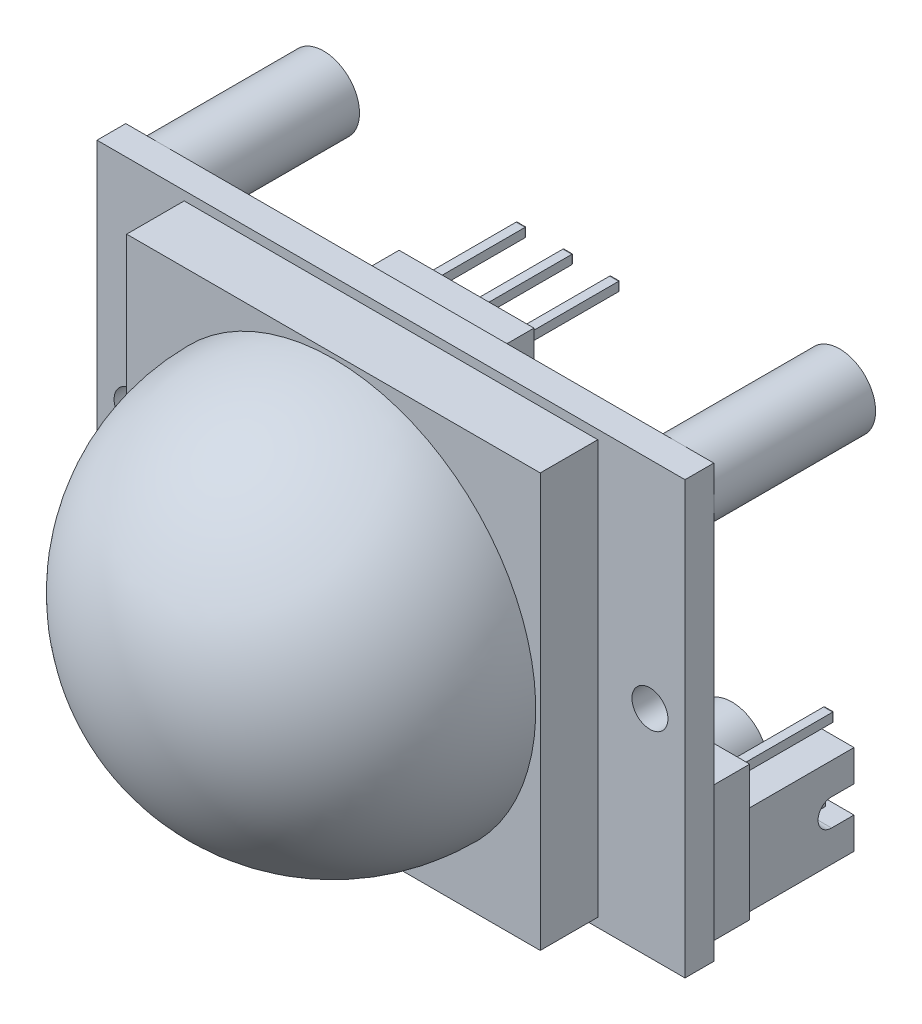
SolidWorks part; units mm, degrees
ref_plane "Front Plane" through (0, 0, 0) normal (0, 0, 1) x (1, 0, 0)
ref_plane "Top Plane" through (0, 0, 0) normal (0, 1, 0) x (1, 0, 0)
ref_plane "Right Plane" through (0, 0, 0) normal (1, 0, 0) x (0, 0, -1)
sketch "Sketch2" plane through (0, 0, 0) normal (0, 0, 1) x (1, 0, 0)
  line L1 (-16.35, 12) -> (16.35, 12)
  line L2 (-16.35, 12) -> (-16.35, -12)
  line L3 (-16.35, -12) -> (16.35, -12)
  line L4 (16.35, 12) -> (16.35, -12)
  line L5 (-16.35, 12) -> (16.35, -12) construction
  line L6 (-16.35, -12) -> (16.35, 12) construction
  point P0 (0, 0)
  dimension "D1" = 32.7
  dimension "D2" = 24
extrude "Boss-Extrude1" add sketch "Sketch2" along normal blind 1.6
sketch "Sketch3" plane through (0, 0, 1.6) normal (0, 0, 1) x (1, 0, 0)
  line L1 (-11.5, 11.5) -> (11.5, 11.5)
  line L2 (-11.5, 11.5) -> (-11.5, -11.5)
  line L3 (-11.5, -11.5) -> (11.5, -11.5)
  line L4 (11.5, 11.5) -> (11.5, -11.5)
  line L5 (-11.5, 11.5) -> (11.5, -11.5) construction
  line L6 (-11.5, -11.5) -> (11.5, 11.5) construction
  point P0 (0, 0)
  dimension "D1" = 23
  dimension "D2" = 23
extrude "Boss-Extrude2" add sketch "Sketch3" along normal blind 3.2
sketch "Sketch4" plane through (0, 0, 4.8) normal (0, 0, 1) x (1, 0, 0)
  circle A0 centre (0, 0) radius 11.25
  dimension "D1" = 22.5
sketch "Sketch5" plane through (0, 0, 0) normal (1, 0, 0) x (0, 0, -1)
  line L0 (-1.6, 0) -> (-16.1, 0) construction
  line L1 (-1.6, -11.5) -> (-1.6, 11.5) construction
  line L2 (-4.825, -0.025) -> (-16.1, 0)
  line L3 (-4.825, -0.025) -> (-4.8, 0)
  line L4 (-1.6, 0) -> (-16.1, 0) construction
  line L5 (-1.6, 0) -> (-4.8, 0) construction
  line L6 (-4.8, 11.25) -> (-4.8, -11.25) construction
  line L7 (-4.8, 0) -> (-4.8, 11.25)
  arc A0 (-4.8, 11.25) -> (-16.1, 0) centre (-4.825, -0.025) ccw
  dimension "D3" = 11.275
  dimension "D1" = 14.5
  dimension "D2" = 11.25
revolve "Revolve2" add sketch "Sketch5" angle 360 about L2
sketch "Sketch6" plane through (0, 0, 1.6) normal (0, 0, 1) x (1, 0, 0)
  line L0 (-16.35, 0) -> (16.35, 0) construction
  line L1 (-16.35, 12) -> (-16.35, -12) construction
  line L2 (16.35, -12) -> (16.35, 12) construction
  line L3 (-14.4, 0) -> (14.4, 0) construction
  circle A0 centre (-14.4, 0) radius 1
  circle A1 centre (14.4, 0) radius 1
  point P10 (0, 0)
  dimension "D1" = 2
  dimension "D2" = 28.8
extrude "Cut-Extrude1" cut sketch "Sketch6" against normal through all
sketch "Sketch7" plane through (0, 0, 0) normal (0, 0, -1) x (-1, 0, 0)
  line L0 (-16.35, 12) -> (16.35, 12) construction
  line L2 (-16.35, -12) -> (-16.35, 12) construction
  line L3 (16.35, 12) -> (16.35, -12) construction
  line L4 (16.35, -12) -> (-16.35, -12) construction
  line L5 (-6.35, -4.6849) -> (-6.35, -14.4498) construction
  circle A0 centre (-14.35, 10) radius 2
  circle A1 centre (14.35, 10) radius 2
  circle A2 centre (14.35, -10) radius 2
  circle A3 centre (-8.35, -10) radius 2
  dimension "D1" = 4
  dimension "D2" = 10
extrude "Boss-Extrude4" add sketch "Sketch7" along normal blind 9
sketch "Sketch8" plane through (0, 0, -9) normal (0, 0, -1) x (-1, 0, 0)
  circle A0 centre (14.35, 10) radius 1
  circle A1 centre (-14.35, 10) radius 1
  arc A2 (-16.35, 10) -> (-14.35, 12) centre (-14.35, 10) ccw construction
  circle A3 centre (14.35, -10) radius 1
  circle A4 centre (14.35, -10) radius 2 construction
  circle A5 centre (-8.35, -10) radius 1
  circle A6 centre (-8.35, -10) radius 2 construction
  dimension "D1" = 2
extrude "Cut-Extrude2" cut sketch "Sketch8" against normal blind 0.3
sketch "Sketch9" plane through (0, 0, 0) normal (0, 0, -1) x (-1, 0, 0)
  line L1 (-9.35, 7.4) -> (-5.35, 7.4)
  line L2 (-9.35, 7.4) -> (-9.35, -3)
  line L3 (-9.35, -3) -> (-5.35, -3)
  line L4 (-5.35, 7.4) -> (-5.35, -3)
  line L5 (-16.35, -12) -> (-16.35, 10) construction
  line L6 (-14.35, 12) -> (14.35, 12) construction
  dimension "D1" = 11
  dimension "D2" = 4.6
  dimension "D3" = 4
  dimension "D4" = 15
extrude "Boss-Extrude5" add sketch "Sketch9" along normal blind 1.5
sketch "Sketch10" plane through (0, 0, 0) normal (0, 0, -1) x (-1, 0, 0)
  line L0 (16.35, 10) -> (16.35, -10) construction
  line L1 (9.85, 4.5) -> (14.35, 4.5)
  line L2 (9.85, 4.5) -> (9.85, 2)
  line L3 (9.85, 2) -> (14.35, 2)
  line L4 (14.35, 4.5) -> (14.35, 2)
  line L5 (-14.35, 12) -> (14.35, 12) construction
  dimension "D1" = 4.5
  dimension "D2" = 2.5
  dimension "D3" = 6.5
  dimension "D4" = 10
extrude "Boss-Extrude6" add sketch "Sketch10" along normal blind 1.5
sketch "Sketch11" plane through (0, 0, 0) normal (0, 0, -1) x (-1, 0, 0)
  line L0 (-16.35, -12) -> (-16.35, 10) construction
  line L1 (-3.85, 11) -> (3.65, 11)
  line L2 (-3.85, 11) -> (-3.85, 8.5)
  line L3 (-3.85, 8.5) -> (3.65, 8.5)
  line L4 (3.65, 11) -> (3.65, 8.5)
  line L5 (-14.35, 12) -> (14.35, 12) construction
  dimension "D1" = 2.5
  dimension "D2" = 7.5
  dimension "D3" = 20
  dimension "D4" = 1
extrude "Boss-Extrude7" add sketch "Sketch11" along normal blind 2.5
sketch "Sketch12" plane through (0, 0, -2.5) normal (0, 0, -1) x (-1, 0, 0)
  line L0 (-3.85, 9.75) -> (3.65, 9.75) construction
  line L1 (-3.85, 11) -> (-3.85, 8.5) construction
  line L2 (3.65, 8.5) -> (3.65, 11) construction
  line L3 (-0.1, 8.5) -> (-0.1, 11) construction
  line L4 (-3.85, 8.5) -> (3.65, 8.5) construction
  line L5 (3.65, 11) -> (-3.85, 11) construction
  line L6 (2.75, 9.75) -> (-2.95, 9.75) construction
  line L7 (-0.35, 10) -> (0.15, 10)
  line L8 (-0.35, 10) -> (-0.35, 9.5)
  line L9 (-0.35, 9.5) -> (0.15, 9.5)
  line L10 (0.15, 10) -> (0.15, 9.5)
  line L11 (-0.35, 10) -> (0.15, 9.5) construction
  line L12 (-0.35, 9.5) -> (0.15, 10) construction
  line L13 (-2.95, 10) -> (-2.45, 10)
  line L14 (-2.95, 10) -> (-2.95, 9.5)
  line L15 (-2.95, 9.5) -> (-2.45, 9.5)
  line L16 (-2.45, 10) -> (-2.45, 9.5)
  line L17 (-2.95, 10) -> (-2.45, 9.5) construction
  line L18 (-2.95, 9.5) -> (-2.45, 10) construction
  line L19 (2.25, 10) -> (2.75, 10)
  line L20 (2.25, 10) -> (2.25, 9.5)
  line L21 (2.25, 9.5) -> (2.75, 9.5)
  line L22 (2.75, 10) -> (2.75, 9.5)
  line L23 (2.25, 10) -> (2.75, 9.5) construction
  line L24 (2.25, 9.5) -> (2.75, 10) construction
  point P12 (-0.1, 9.75)
  point P20 (-0.1, 9.75)
  point P21 (-2.7, 9.75)
  point P26 (-2.7, 9.75)
  point P27 (2.5, 9.75)
  point P32 (2.5, 9.75)
  dimension "D1" = 0.5
  dimension "D2" = 0.5
  dimension "D3" = 5.7
extrude "Boss-Extrude8" add sketch "Sketch12" along normal blind 5.7
fillet "Fillet1" radius 0.1 12 edges at (-2.5, 9.5, -8.2) (-2.25, 9.75, -8.2) (-2.5, 10, -8.2) (-2.75, 9.75, -8.2) (0.1, 9.5, -8.2) (-0.15, 9.75, -8.2) (0.1, 10, -8.2) (0.35, 9.75, -8.2) (2.7, 9.5, -8.2) (2.95, 9.75, -8.2) (2.45, 9.75, -8.2) (2.7, 10, -8.2)
sketch "Sketch13" plane through (0, 0, 0) normal (0, 0, -1) x (-1, 0, 0)
  line L0 (-16.35, -12) -> (-16.35, 10) construction
  line L1 (-13.35, -11.5) -> (-15.85, -11.5)
  line L2 (-13.35, -11.5) -> (-13.35, -4)
  line L3 (-13.35, -4) -> (-15.85, -4)
  line L4 (-15.85, -11.5) -> (-15.85, -4)
  line L5 (-8.35, -12) -> (-16.35, -12) construction
  dimension "D1" = 7.5
  dimension "D2" = 2.5
  dimension "D3" = 0.5
  dimension "D4" = 0.5
extrude "Boss-Extrude9" add sketch "Sketch13" along normal blind 2.5
sketch "Sketch14" plane through (0, 0, -2.5) normal (0, 0, -1) x (-1, 0, 0)
  line L0 (-15.85, -4) -> (-15.85, -11.5) construction
  line L1 (-13.15, -11.3) -> (-15.65, -11.3)
  line L2 (-13.15, -11.3) -> (-13.15, -6.3)
  line L3 (-13.15, -6.3) -> (-15.65, -6.3)
  line L4 (-15.65, -11.3) -> (-15.65, -6.3)
  line L7 (-15.85, -11.5) -> (-13.35, -11.5) construction
  dimension "D1" = 5
  dimension "D2" = 2.5
  dimension "D3" = 0.2
  dimension "D4" = 0.2
extrude "Boss-Extrude10" add sketch "Sketch14" along normal blind 6
sketch "Sketch17" plane through (15.65, 0, 0) normal (1, 0, 0) x (0, 0, -1)
  line L0 (8.5, -8.8) -> (2.5, -8.8) construction
  line L1 (8.5, -6.3) -> (8.5, -11.3) construction
  line L2 (2.5, -6.3) -> (2.5, -11.3) construction
  line L3 (8.5, -8.8) -> (6.5, -8.8) construction
  line L4 (8.5, -8.05) -> (7.3244, -8.05)
  line L5 (8.5, -8.05) -> (8.5, -9.55)
  line L6 (8.5, -9.55) -> (7.3244, -9.55)
  line L7 (7.3244, -8.05) -> (7.3244, -8.0537)
  line L10 (6.5, -7.0903) -> (6.5, -10.3644) construction
  line L11 (5.5, -8.8) -> (4.6684, -8.8) construction
  line L12 (7.3244, -9.5463) -> (7.3244, -9.55)
  line L13 (7.3276, -8.054) -> (7.3244, -8.05) construction
  line L14 (7.3276, -9.546) -> (7.3244, -9.55) construction
  arc A3 (7.3276, -8.054) -> (7.3244, -8.0537) centre (7.25, -8.8) ccw
  arc A4 (7.3276, -8.054) -> (7.3244, -8.0537) centre (7.25, -8.8) ccw
  arc A5 (7.3244, -9.5463) -> (7.3276, -9.546) centre (7.25, -8.8) ccw
  arc A6 (7.3244, -9.5463) -> (7.3276, -9.546) centre (7.25, -8.8) ccw
  arc A7 (7.3276, -8.054) -> (7.3276, -9.546) centre (7.25, -8.8) ccw
  point P6 (7.9122, -8.8)
  point P16 (5.5, -9.3356)
  line M10 (8.5, -11.3) -> (8.5, -6.3)
  dimension "D1" = 1.5
  dimension "D2" = 2
extrude "Cut-Extrude3" cut sketch "Sketch17" against normal blind 4 contours A7 L12 L6 L4 L7 M10 region at (15.65, -8.8, -7.5729)
ref_plane "Plane1" through (0, 0, -8.1) normal (0, 0, -1) x (-1, 0, 0)
sketch "Sketch18" plane through (0, 0, -8.1) normal (0, 0, -1) x (-1, 0, 0)
  line L4 (-13.15, -9.5463) -> (-15.65, -9.5463) construction
  line L5 (-14.45, -8.0537) -> (-14.45, -9.5463)
  line L6 (-14.35, -8.0537) -> (-14.35, -9.5463)
  line L7 (-13.15, -8.0537) -> (-15.65, -8.0537) construction
  line L8 (-14.35, -8.0537) -> (-14.45, -8.0537)
  line L9 (-14.35, -9.5463) -> (-14.45, -9.5463)
  point P0 (0, 0)
extrude "Boss-Extrude11" add sketch "Sketch18" against normal blind 0.7 separate body
other "DeleteFace1" face at (14.4, -9.5481, -7.3244) face at (14.4, -8.0519, -7.3244) and patch yes
sketch "Sketch19" plane through (0, 0, -2.5) normal (0, 0, -1) x (-1, 0, 0)
  line L0 (-14.6, -4) -> (-14.6, -11.5) construction
  line L1 (-13.35, -4) -> (-15.85, -4) construction
  line L2 (-15.85, -11.5) -> (-13.35, -11.5) construction
  line L3 (-15.65, -11.3) -> (-13.35, -11.3) construction
  line L4 (-14.35, -4.8) -> (-14.85, -4.8)
  line L5 (-14.35, -4.8) -> (-14.35, -5.3)
  line L6 (-14.35, -5.3) -> (-14.85, -5.3)
  line L7 (-14.85, -4.8) -> (-14.85, -5.3)
  line L8 (-14.35, -4.8) -> (-14.85, -5.3) construction
  line L9 (-14.35, -5.3) -> (-14.85, -4.8) construction
  point P6 (-14.6, -5.05)
  dimension "D1" = 6.5
  dimension "D2" = 0.5
  dimension "D3" = 0.5
extrude "Boss-Extrude12" add sketch "Sketch19" along normal blind 5.7
fillet "Fillet2" radius 0.1 4 edges at (14.35, -5.05, -8.2) (14.6, -5.3, -8.2) (14.6, -4.8, -8.2) (14.85, -5.05, -8.2)
sketch "Sketch20" plane through (0, 0, 0) normal (0, 0, -1) x (-1, 0, 0)
  line L0 (-16.35, -12) -> (-16.35, 10) construction
  line L1 (0.15, -9.5) -> (-5.35, -9.5)
  line L2 (0.15, -9.5) -> (0.15, -6.5)
  line L3 (0.15, -6.5) -> (-5.35, -6.5)
  line L4 (-5.35, -9.5) -> (-5.35, -6.5)
  line L5 (14.35, -12) -> (-8.35, -12) construction
  dimension "D1" = 16.5
  dimension "D2" = 5.5
  dimension "D3" = 3
  dimension "D4" = 2.5
extrude "Boss-Extrude13" add sketch "Sketch20" along normal blind 7.5
sketch "Sketch21" plane through (0, -9.5, 0) normal (0, -1, 0) x (1, 0, 0)
  line L0 (4.35, -7.1) -> (0.85, -7.1)
  line L1 (2.6, -7.1) -> (2.6, -4.7) construction
  line L2 (-0.15, -3.75) -> (5.35, -3.75) construction
  line L3 (-0.15, -7.5) -> (-0.15, 0) construction
  line L4 (5.35, -7.5) -> (5.35, 0) construction
  line L5 (2.6, -3.75) -> (2.6, -7.5) construction
  line L6 (5.35, -7.5) -> (-0.15, -7.5) construction
  line L7 (4.874, -2.4) -> (-1.4751, -2.4) construction
  line L8 (4.35, -7.1) -> (4.35, -6.1925)
  line L9 (0.85, -7.1) -> (0.85, -6.1925)
  arc A0 (4.35, -6.1925) -> (0.85, -6.1925) centre (2.6, -4.7) ccw
  dimension "D1" = 4.6
  dimension "D2" = 3.5
  dimension "D3" = 4.7
  dimension "D4" = 0.4
extrude "Boss-Extrude14" add sketch "Sketch21" along normal blind 1
sketch "Sketch23" plane through (0, -10.5, 0) normal (0, -1, 0) x (1, 0, 0)
  line L0 (2.6, -4.7) -> (2.6, -7.1) construction
  line L1 (0.85, -7.1) -> (4.35, -7.1) construction
  line L2 (2.6, -7.1) -> (2.6, -2.4) construction
  line L3 (2.6, -4.7) -> (0.3, -4.7) construction
  line L4 (0.3, -4.7) -> (4.9, -4.7) construction
  line L5 (2.6, -6.4) -> (2.6, -3)
  line L6 (3, -6.4) -> (3, -3)
  line L7 (2.2, -6.4) -> (2.2, -3)
  line L8 (3, -6.4) -> (2.2, -6.4)
  line L9 (3, -3) -> (2.2, -3)
  line L10 (4.3, -4.7) -> (0.9, -4.7)
  line L11 (4.3, -4.3) -> (0.9, -4.3)
  line L12 (4.3, -5.1) -> (0.9, -5.1)
  line L13 (4.3, -4.3) -> (4.3, -5.1)
  line L14 (0.9, -4.3) -> (0.9, -5.1)
  arc A1 (4.35, -6.1925) -> (0.85, -6.1925) centre (2.6, -4.7) ccw construction
  arc A2 (4.35, -6.1925) -> (0.85, -6.1925) centre (2.6, -4.7) ccw construction
  point P17 (2.6, -4.7)
  point P24 (2.6, -4.7)
  dimension "D1" = 3.4
  dimension "D4" = 3.4
  dimension "D2" = 0.4
  dimension "D3" = 0.4
  dimension "D5" = 0.4
  dimension "D6" = 0.4
extrude "Cut-Extrude4" cut sketch "Sketch23" against normal blind 1.8 contours L6 L12 L5 L8 | L5 L12 L7 L8 | L12 L5 L10 L7 | L12 L6 L10 L5 | L6 L11 L5 L10 | L5 L11 L7 L10 | L10 L14 L12 L7 | L11 L14 L10 L7 | L11 L5 L9 L7 | L11 L6 L9 L5 | L13 L11 L6 L10 | L13 L10 L6 L12 region at (2.4, -10.5, -5.75) region at (2.8, -10.5, -5.75) region at (2.4, -10.5, -4.9) region at (2.8, -10.5, -4.9) region at (2.4, -10.5, -4.5) region at (2.8, -10.5, -4.5) region at (3.65, -10.5, -4.9) region at (1.55, -10.5, -4.9) region at (2.4, -10.5, -3.65) region at (2.8, -10.5, -3.65) region at (3.65, -10.5, -4.5) region at (1.55, -10.5, -4.5)
sketch "Sketch24" plane through (0, 0, 0) normal (0, 0, -1) x (-1, 0, 0)
  line L0 (-5.35, -9.5) -> (0.15, -9.5) construction
  line L1 (3.85, -6.5) -> (9.35, -6.5)
  line L2 (3.85, -6.5) -> (3.85, -9.5)
  line L3 (3.85, -9.5) -> (9.35, -9.5)
  line L4 (9.35, -6.5) -> (9.35, -9.5)
  line L5 (0.15, -6.5) -> (-5.35, -6.5) construction
  line L7 (16.35, 10) -> (16.35, -10) construction
  dimension "D1" = 5.5
  dimension "D2" = 12.5
extrude "Boss-Extrude15" add sketch "Sketch24" along normal up to surface (7.5 mm away) up to face at (2.6, -8, -7.5)
ref_plane "Plane2" through (-2, 0, 0) normal (1, 0, 0) x (0, 0, -1)
mirror "Mirror1" about plane through (-2, 0, 0) normal (1, 0, 0) of "Cut-Extrude4", "Boss-Extrude14"
